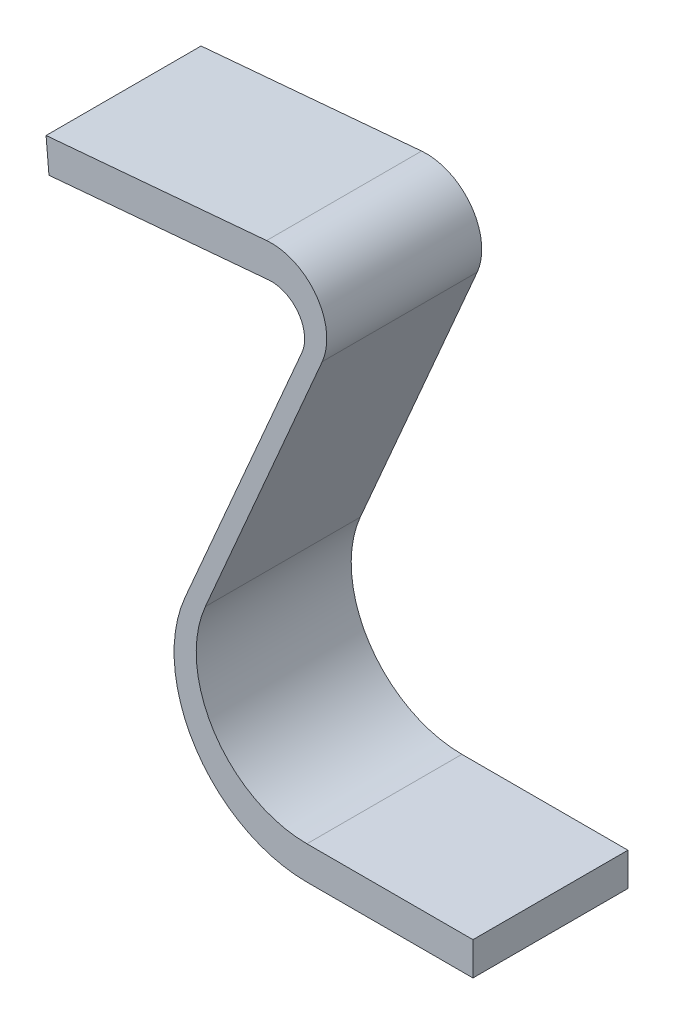
SolidWorks part; units mm, degrees
ref_plane "Front Plane" through (0, 0, 0) normal (0, 0, 1) x (1, 0, 0)
ref_plane "Top Plane" through (0, 0, 0) normal (0, 1, 0) x (1, 0, 0)
ref_plane "Right Plane" through (0, 0, 0) normal (1, 0, 0) x (0, 0, -1)
sketch "Sketch1" plane through (0, 0, 0) normal (0, 0, 1) x (1, 0, 0)
  line L0 (-17.4584, -11.3648) -> (2.4655, -9.6217)
  line L1 (7.4911, -16.586) -> (-3.0728, -41.0334)
  line L3 (6.1069, -55) -> (21.1069, -55)
  line L4 (-17.1973, -14.3496) -> (2.6398, -12.6141)
  line L5 (5.6552, -16.7927) -> (-4.9087, -41.2401)
  line L6 (6.1069, -58) -> (21.1069, -58)
  line L7 (-17.4584, -11.3648) -> (-17.1973, -14.3496)
  line L8 (21.1069, -55) -> (21.1069, -58)
  arc A0 (7.4911, -16.586) -> (2.4655, -9.6217) centre (2.9013, -14.6027) ccw
  arc A1 (6.1069, -55) -> (-3.0728, -41.0334) centre (6.1069, -45) cw
  arc A2 (5.6552, -16.7927) -> (2.6398, -12.6141) centre (2.9013, -15.6027) ccw
  arc A3 (6.1069, -58) -> (-4.9087, -41.2401) centre (6.1069, -46) cw
  point P10 (10.8161, -8.8912)
  point P13 (-9.1078, -55)
  dimension "D1" = 5
  dimension "D2" = 10
  dimension "D3" = 15
  dimension "D4" = 20
  dimension "D5" = 3
extrude "Boss-Extrude1" add sketch "Sketch1" along normal blind 7 and the other way blind 7
